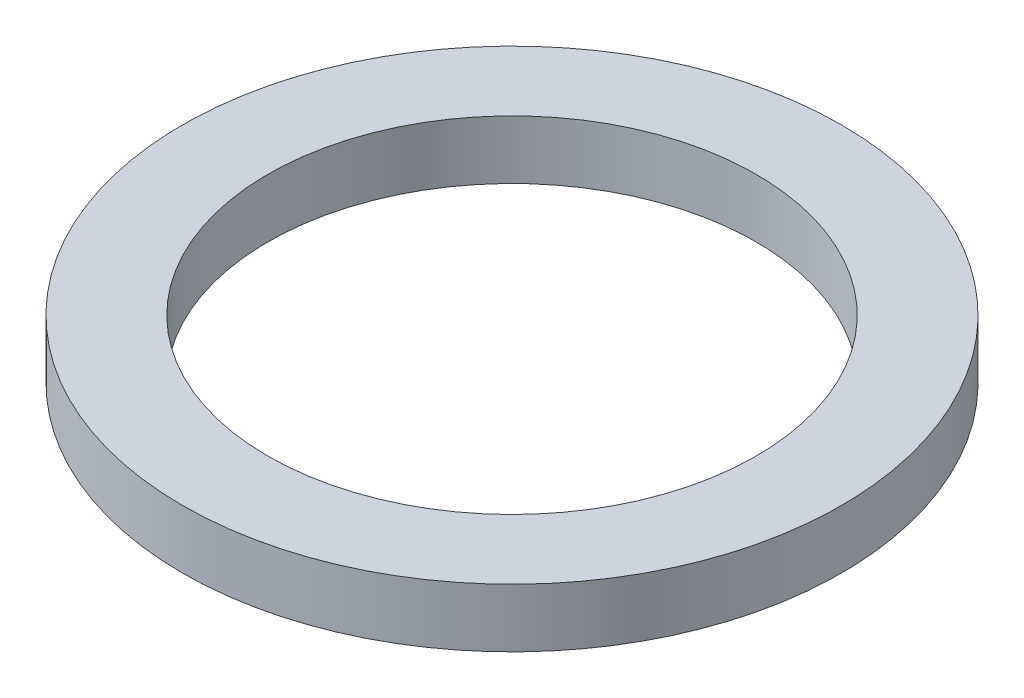
SolidWorks part; units mm, degrees
ref_plane "Front Plane" through (0, 0, 0) normal (0, 0, 1) x (1, 0, 0)
ref_plane "Top Plane" through (0, 0, 0) normal (0, 1, 0) x (1, 0, 0)
ref_plane "Right Plane" through (0, 0, 0) normal (1, 0, 0) x (0, 0, -1)
sketch "Sketch1" plane through (0, 0, 0) normal (0, 1, 0) x (1, 0, 0)
  circle A0 centre (0, 0) radius 67.5
  dimension "FLANGE_OD" = 135
extrude "Boss-Extrude1" add sketch "Sketch1" along normal blind 12
sketch "Sketch2" plane through (0, 0, 0) normal (0, 1, 0) x (1, 0, 0)
  circle A0 centre (0, 0) radius 50
  dimension "BORE_D" = 100
extrude "Cut-Extrude1" cut sketch "Sketch2" along normal through all
sketch "Sketch3" plane through (0, 12, 0) normal (0, 1, 0) x (1, 0, 0)
  circle A0 centre (0, 0) radius 27.686 construction
  circle A1 centre (-27.686, 0) radius 2.8884
  dimension "BOLT_D" = 5.7769
  dimension "BOLT_PCD" = 55.3719
extrude "Cut-Extrude2" cut sketch "Sketch3" against normal blind 9.4422 rebuild error yes
pattern_circular "CirPattern1" count 6 over 360 rebuild error yes
